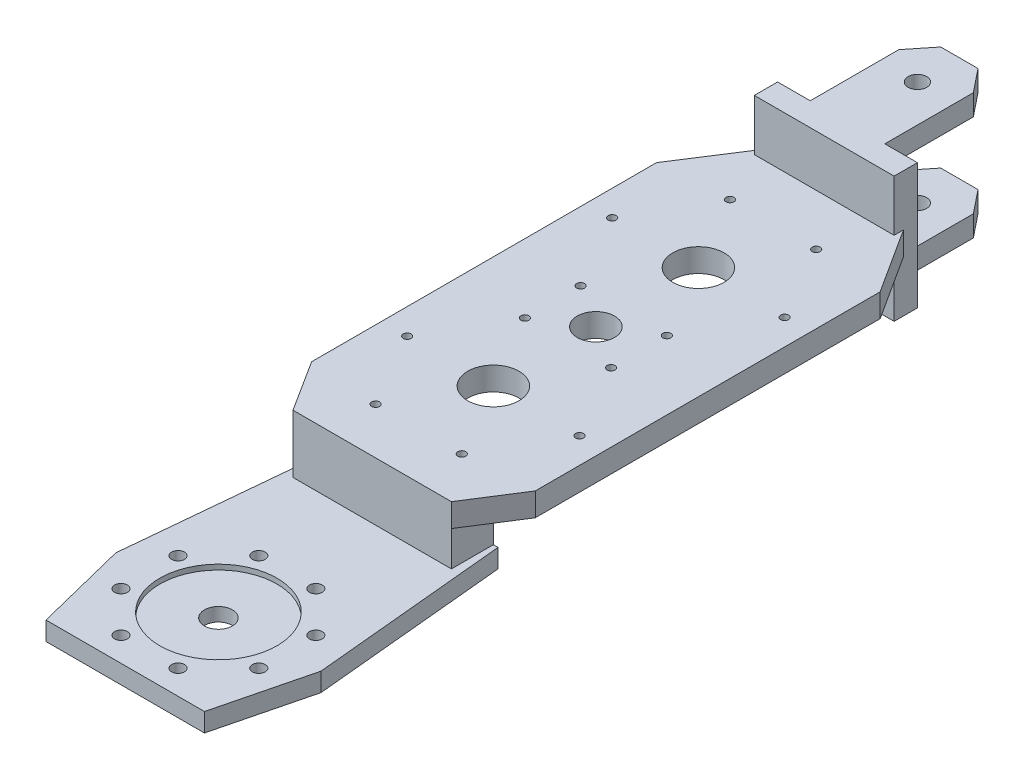
SolidWorks part; units mm, degrees
ref_plane "Front Plane" through (0, 0, 0) normal (0, 0, 1) x (1, 0, 0)
ref_plane "Top Plane" through (0, 0, 0) normal (0, 1, 0) x (1, 0, 0)
ref_plane "Right Plane" through (0, 0, 0) normal (1, 0, 0) x (0, 0, -1)
ref_plane "PL_Knee_Plate_base" through (0, -28, 0) normal (0, 1, 0) x (1, 0, 0)
sketch "SK_Knee_Plate" plane through (0, -28, 0) normal (0, 1, 0) x (1, 0, 0)
  line L0 (-34, -40) -> (34, -40)
  line L1 (34, -40) -> (44, 0)
  line L2 (44, 0) -> (36, 84)
  line L3 (36, 84) -> (-36, 84)
  line L4 (-36, 84) -> (-44, 0)
  line L5 (-44, 0) -> (-34, -40)
  circle A0 centre (29.5641, 12.2459) radius 2.75
  circle A1 centre (12.2459, 29.5641) radius 2.75
  circle A2 centre (-12.2459, 29.5641) radius 2.75
  circle A3 centre (-29.5641, 12.2459) radius 2.75
  circle A4 centre (-29.5641, -12.2459) radius 2.75
  circle A5 centre (-12.2459, -29.5641) radius 2.75
  circle A6 centre (12.2459, -29.5641) radius 2.75
  circle A7 centre (29.5641, -12.2459) radius 2.75
  circle A8 centre (0, 0) radius 6
  dimension "D11_SK_Knee_Plate" = 5.5
  dimension "D14_SK_Knee_Plate" = 5.5
  dimension "D17_SK_Knee_Plate" = 5.5
  dimension "D20_SK_Knee_Plate" = 5.5
  dimension "D23_SK_Knee_Plate" = 5.5
  dimension "D26_SK_Knee_Plate" = 5.5
  dimension "D29_SK_Knee_Plate" = 5.5
  dimension "D32_SK_Knee_Plate" = 5.5
  dimension "D35_SK_Knee_Plate" = 12
  dimension "P1" = 34
  dimension "P2" = 40
  dimension "P3" = 34
  dimension "P4" = 40
  dimension "P5" = 44
  dimension "P6" = 36
  dimension "P7" = 84
  dimension "P8" = 36
  dimension "P9" = 84
  dimension "P10" = 44
  dimension "P12" = 29.5641
  dimension "P13" = 12.2459
  dimension "P15" = 12.2459
  dimension "P16" = 29.5641
  dimension "P18" = 12.2459
  dimension "P19" = 29.5641
  dimension "P21" = 29.5641
  dimension "P22" = 12.2459
  dimension "P24" = 29.5641
  dimension "P25" = 12.2459
  dimension "P27" = 12.2459
  dimension "P28" = 29.5641
  dimension "P30" = 12.2459
  dimension "P31" = 29.5641
  dimension "P33" = 29.5641
  dimension "P34" = 12.2459
extrude "Knee_Plate" add sketch "SK_Knee_Plate" along normal blind 8
ref_plane "PL_Knee_Pilot_Recess_base" through (0, -20, 0) normal (0, 1, 0) x (1, 0, 0)
sketch "SK_Knee_Pilot_Recess" plane through (0, -20, 0) normal (0, 1, 0) x (1, 0, 0)
  circle A0 centre (0, 0) radius 25.15
  dimension "D1_SK_Knee_Pilot_Recess" = 50.3
extrude "Knee_Pilot_Recess" cut sketch "SK_Knee_Pilot_Recess" against normal blind 2.2
ref_plane "PL_Joggle_base" through (0, 0, -84) normal (0, 0, 1) x (1, 0, 0)
sketch "SK_Joggle" plane through (0, 0, -84) normal (0, 0, 1) x (1, 0, 0)
  line L0 (-34, -28) -> (34, -28)
  line L1 (34, -28) -> (34, 5)
  line L2 (34, 5) -> (-34, 5)
  line L3 (-34, 5) -> (-34, -28)
  dimension "P1" = 34
  dimension "P2" = 28
  dimension "P3" = 34
  dimension "P4" = 28
  dimension "P5" = 34
  dimension "P6" = 5
  dimension "P7" = 34
  dimension "P8" = 5
extrude "Joggle" add sketch "SK_Joggle" along normal blind 18
ref_plane "PL_Web_base" through (0, -5, 0) normal (0, 1, 0) x (1, 0, 0)
sketch "SK_Web" plane through (0, -5, 0) normal (0, 1, 0) x (1, 0, 0)
  line L0 (-34, 66) -> (34, 66)
  line L1 (34, 66) -> (48, 88)
  line L2 (48, 88) -> (48, 236)
  line L3 (48, 236) -> (30, 264)
  line L4 (30, 264) -> (-30, 264)
  line L5 (-30, 264) -> (-48, 236)
  line L6 (-48, 236) -> (-48, 88)
  line L7 (-48, 88) -> (-34, 66)
  circle A0 centre (37, 118) radius 1.7
  circle A1 centre (18.5, 150.0429) radius 1.7
  circle A2 centre (-18.5, 150.0429) radius 1.7
  circle A3 centre (-37, 118) radius 1.7
  circle A4 centre (-18.5, 85.9571) radius 1.7
  circle A5 centre (18.5, 85.9571) radius 1.7
  circle A6 centre (37, 206) radius 1.7
  circle A7 centre (18.5, 238.0429) radius 1.7
  circle A8 centre (-18.5, 238.0429) radius 1.7
  circle A9 centre (-37, 206) radius 1.7
  circle A10 centre (-18.5, 173.9571) radius 1.7
  circle A11 centre (18.5, 173.9571) radius 1.7
  circle A12 centre (0, 118) radius 11
  circle A13 centre (0, 206) radius 11
  circle A14 centre (0, 162) radius 8
  dimension "D17_SK_Web" = 3.4
  dimension "D20_SK_Web" = 3.4
  dimension "D23_SK_Web" = 3.4
  dimension "D26_SK_Web" = 3.4
  dimension "D29_SK_Web" = 3.4
  dimension "D32_SK_Web" = 3.4
  dimension "D35_SK_Web" = 3.4
  dimension "D38_SK_Web" = 3.4
  dimension "D41_SK_Web" = 3.4
  dimension "D44_SK_Web" = 3.4
  dimension "D47_SK_Web" = 3.4
  dimension "D50_SK_Web" = 3.4
  dimension "D53_SK_Web" = 22
  dimension "D55_SK_Web" = 22
  dimension "D57_SK_Web" = 16
  dimension "P1" = 34
  dimension "P2" = 66
  dimension "P3" = 34
  dimension "P4" = 66
  dimension "P5" = 48
  dimension "P6" = 88
  dimension "P7" = 48
  dimension "P8" = 236
  dimension "P9" = 30
  dimension "P10" = 264
  dimension "P11" = 30
  dimension "P12" = 264
  dimension "P13" = 48
  dimension "P14" = 236
  dimension "P15" = 48
  dimension "P16" = 88
  dimension "P18" = 37
  dimension "P19" = 118
  dimension "P21" = 18.5
  dimension "P22" = 150.0429
  dimension "P24" = 18.5
  dimension "P25" = 150.0429
  dimension "P27" = 37
  dimension "P28" = 118
  dimension "P30" = 18.5
  dimension "P31" = 85.9571
  dimension "P33" = 18.5
  dimension "P34" = 85.9571
  dimension "P36" = 37
  dimension "P37" = 206
  dimension "P39" = 18.5
  dimension "P40" = 238.0429
  dimension "P42" = 18.5
  dimension "P43" = 238.0429
  dimension "P45" = 37
  dimension "P46" = 206
  dimension "P48" = 18.5
  dimension "P49" = 173.9571
  dimension "P51" = 18.5
  dimension "P52" = 173.9571
  dimension "P54" = 118
  dimension "P56" = 206
  dimension "P58" = 162
extrude "Web" add sketch "SK_Web" along normal blind 10
ref_plane "PL_Fork_Bar_base" through (0, 0, -270) normal (0, 0, 1) x (1, 0, 0)
sketch "SK_Fork_Bar" plane through (0, 0, -270) normal (0, 0, 1) x (1, 0, 0)
  line L0 (-30, -27) -> (30, -27)
  line L1 (30, -27) -> (30, 27)
  line L2 (30, 27) -> (-30, 27)
  line L3 (-30, 27) -> (-30, -27)
  dimension "P1" = 30
  dimension "P2" = 27
  dimension "P3" = 30
  dimension "P4" = 27
  dimension "P5" = 30
  dimension "P6" = 27
  dimension "P7" = 30
  dimension "P8" = 27
extrude "Fork_Bar" add sketch "SK_Fork_Bar" along normal blind 10
ref_plane "PL_Tine_Lat_base" through (0, 18, 0) normal (0, 1, 0) x (1, 0, 0)
sketch "SK_Tine_Lat" plane through (0, 18, 0) normal (0, 1, 0) x (1, 0, 0)
  line L0 (-16, 260) -> (16, 260)
  line L1 (16, 260) -> (16, 308)
  line L2 (16, 308) -> (8, 318)
  line L3 (8, 318) -> (-8, 318)
  line L4 (-8, 318) -> (-16, 308)
  line L5 (-16, 308) -> (-16, 260)
  circle A0 centre (0, 300) radius 4
  dimension "D13_SK_Tine_Lat" = 8
  dimension "P1" = 16
  dimension "P2" = 260
  dimension "P3" = 16
  dimension "P4" = 260
  dimension "P5" = 16
  dimension "P6" = 308
  dimension "P7" = 8
  dimension "P8" = 318
  dimension "P9" = 8
  dimension "P10" = 318
  dimension "P11" = 16
  dimension "P12" = 308
  dimension "P14" = 300
extrude "Tine_Lat" add sketch "SK_Tine_Lat" along normal blind 9
ref_plane "PL_Tine_Med_base" through (0, -27, 0) normal (0, 1, 0) x (1, 0, 0)
sketch "SK_Tine_Med" plane through (0, -27, 0) normal (0, 1, 0) x (1, 0, 0)
  line L0 (-16, 260) -> (16, 260)
  line L1 (16, 260) -> (16, 308)
  line L2 (16, 308) -> (8, 318)
  line L3 (8, 318) -> (-8, 318)
  line L4 (-8, 318) -> (-16, 308)
  line L5 (-16, 308) -> (-16, 260)
  circle A0 centre (0, 300) radius 4
  dimension "D13_SK_Tine_Med" = 8
  dimension "P1" = 16
  dimension "P2" = 260
  dimension "P3" = 16
  dimension "P4" = 260
  dimension "P5" = 16
  dimension "P6" = 308
  dimension "P7" = 8
  dimension "P8" = 318
  dimension "P9" = 8
  dimension "P10" = 318
  dimension "P11" = 16
  dimension "P12" = 308
  dimension "P14" = 300
extrude "Tine_Med" add sketch "SK_Tine_Med" along normal blind 9
ref_plane "PL_AnkleZ" through (0, 0, -300) normal (0, 0, 1) x (1, 0, 0)
ref_axis "AX_AnklePitch" through (0, 29.75, -300) along (0, -1, 0)
ref_axis "AX_KneeY" through (0, 29.75, 0) along (0, -1, 0)
ref_plane "PL_KneeRef" through (0, 0, 0) normal (-0.9239, 0, 0.3827) x (0, -1, 0)
equation "\"Shin_length\" = 300"
equation "\"AnkleA_z\" = -118"
equation "\"AnkleB_z\" = -206"
